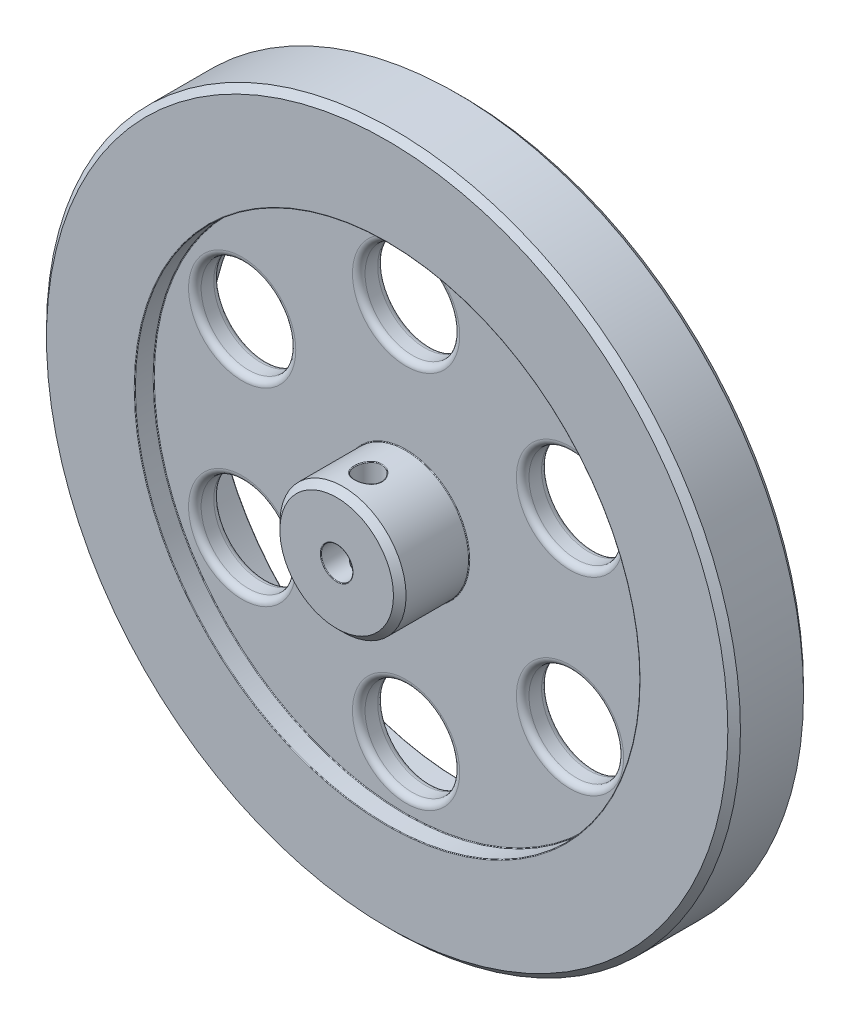
SolidWorks part; units mm, degrees
ref_plane "Front Plane" through (0, 0, 0) normal (0, 0, 1) x (1, 0, 0)
ref_plane "Top Plane" through (0, 0, 0) normal (0, 1, 0) x (1, 0, 0)
ref_plane "Right Plane" through (0, 0, 0) normal (1, 0, 0) x (0, 0, -1)
sketch "Sketch1" plane through (0, 0, 0) normal (0, 0, 1) x (1, 0, 0)
  line L0 (0, 0) -> (0, 30) construction
  circle A0 centre (0, 0) radius 55
  circle A1 centre (0, 0) radius 40
  circle A2 centre (0, 0) radius 30 construction
  circle A3 centre (0, 0) radius 10
  circle A4 centre (0, 30) radius 7.5
  circle A5 centre (25.9808, 15) radius 7.5
  circle A6 centre (25.9808, -15) radius 7.5
  circle A7 centre (0, -30) radius 7.5
  circle A8 centre (-25.9808, -15) radius 7.5
  circle A9 centre (-25.9808, 15) radius 7.5
  circle A10 centre (0, 0) radius 2.5
  dimension "D1" = 110
  dimension "D2" = 80
  dimension "D3" = 60
  dimension "D4" = 20
  dimension "D5" = 15
  dimension "D7" = 5
  dimension "D6" = 6
extrude "Boss-Extrude1" add sketch "Sketch1" along normal blind 12 contours A0 A1 region at (-53.4444, 0, 0)
extrude "Boss-Extrude2" add sketch "Sketch1<3>" along normal blind 4 from offset 5 contours A1 A9 A8 A7 A6 A5 A4 A3 region at (-38.8686, 0, 0)
sketch "Sketch1<3>" plane through (0, 0, 0) normal (0, 0, 1) x (1, 0, 0) same geometry as "Sketch1"
extrude "Boss-Extrude3" add sketch "Sketch1<4>" along normal blind 15 from offset 5 contours A3 A10 region at (-9.7172, 0, 0)
sketch "Sketch1<4>" plane through (0, 0, 0) normal (0, 0, 1) x (1, 0, 0) same geometry as "Sketch1"
hole_wizard "M5x0.8 Tapped Hole1" positions "Sketch2" profile "Sketch3" tap size "M5x0.8" standard "ANSI Metric"
sketch "Sketch2" plane through (0, 0, 0) normal (0, 1, 0) x (1, 0, 0)
  point P0 (0, -15)
  point P5 (0, -16.159)
  dimension "D1" = 5
sketch "Sketch3" plane through (0, 0, 15) normal (1, 0, 0) x (0, 0, 1)
  line L0 (0, 0) -> (0, 11.2618)
  line L1 (0, 11.2618) -> (2.1, 10)
  line L2 (2.1, 10) -> (2.1, 0)
  line L5 (2.1, 0) -> (0, 0)
  line L10 (0, 11.2618) -> (-2.1, 10) construction
  line L11 (0, -6.35) -> (0, 107.95) construction
  dimension "Tap Drill Dia." = 4.2
  dimension "Tap Drill Depth" = 10
  dimension "Drill Angle" = 118
mirror "Mirror2" about plane through (0, 0, 0) normal (0, 1, 0) of "M5x0.8 Tapped Hole1"
chamfer "Chamfer1" distance 1 angle 45 3 edges at (10, 0, 20) (55, 0, 0) (55, 0, 12)
fillet "Fillet1" radius 0.1 8 edges at (40, 0, 0) (40, 0, 5) (40, 0, 9) (40, 0, 12) (-0.4316, -9.9907, 12.9448) (2.5, 0, 20) (-0.4316, 9.9907, 17.0552) (10, 0, 9)
fillet "Fillet2" radius 1 12 edges at (-18.4808, 15, 5) (33.4808, -15, 5) (33.4808, 15, 5) (7.5, 30, 5) (-18.4808, 15, 9) (-18.4808, -15, 9) (7.5, -30, 9) (33.4808, -15, 9) (33.4808, 15, 9) (7.5, 30, 9) (7.5, -30, 5) (-18.4808, -15, 5)
